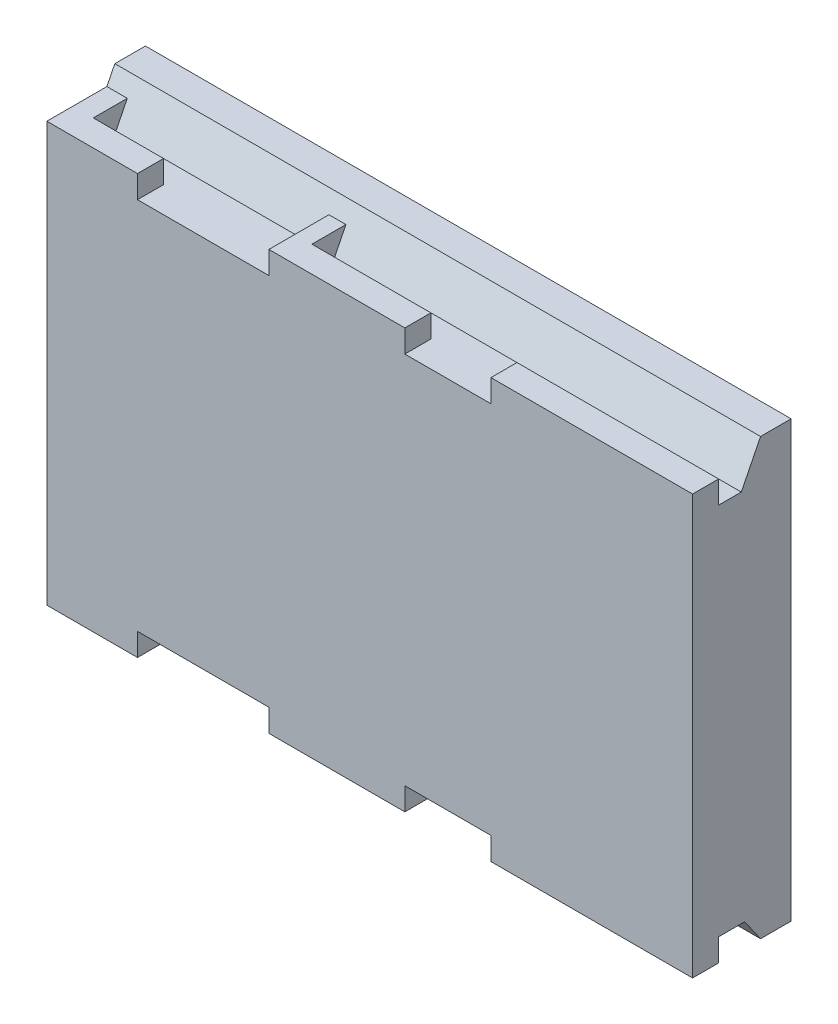
SolidWorks part; units mm, degrees
ref_plane "Спереди" through (0, 0, 0) normal (0, 0, 1) x (1, 0, 0)
ref_plane "Сверху" through (0, 0, 0) normal (0, 1, 0) x (1, 0, 0)
ref_plane "Справа" through (0, 0, 0) normal (1, 0, 0) x (0, 0, -1)
sketch "Эскиз1" plane through (0, 0, 0) normal (0, 0, 1) x (1, 0, 0)
  line L1 (0, 0) -> (57, 0)
  line L2 (0, 0) -> (0, 38.4)
  line L3 (0, 38.4) -> (57, 38.4)
  line L4 (57, 0) -> (57, 38.4)
  dimension "D1" = 57
  dimension "D2" = 38.4
extrude "Бобышка-Вытянуть1" add sketch "Эскиз1" along normal blind 8.7
sketch "Эскиз2" plane through (0, 0, 8.7) normal (0, 0, 1) x (1, 0, 0)
  line L0 (57, 0) -> (57, 38.4) construction
  line L1 (0, 38.4) -> (57, 38.4)
  line L2 (0, 38.4) -> (0, 37)
  line L3 (0, 37) -> (57, 37)
  line L4 (57, 38.4) -> (57, 37)
  line L5 (0, 0) -> (57, 0) construction
  dimension "D1" = 37
extrude "Вырез-Вытянуть1" cut sketch "Эскиз2" against normal blind 2.3
sketch "Эскиз3" plane through (0, 0, 0) normal (0, 1, 0) x (1, 0, 0)
  line L0 (57, -6.4) -> (57, 0) construction
  line L1 (0, -6.4) -> (57, -6.4)
  line L2 (0, -6.4) -> (0, -4.1)
  line L3 (0, -4.1) -> (57, -4.1)
  line L4 (57, -6.4) -> (57, -4.1)
  dimension "D1" = 2.3
extrude "Вырез-Вытянуть2" cut sketch "Эскиз3" along normal blind 2
sketch "Эскиз4" plane through (0, 0, 8.7) normal (0, 0, 1) x (1, 0, 0)
  line L0 (0, 0) -> (57, 0) construction
  line L1 (8, 0) -> (19.6, 0)
  line L2 (8, 0) -> (8, 2)
  line L3 (8, 2) -> (19.6, 2)
  line L4 (19.6, 0) -> (19.6, 2)
  line L5 (0, 2) -> (57, 2) construction
  line L6 (31.6, 0) -> (39.2, 0)
  line L7 (31.6, 0) -> (31.6, 2)
  line L8 (31.6, 2) -> (39.2, 2)
  line L9 (39.2, 0) -> (39.2, 2)
  line L10 (0, 37) -> (0, 0) construction
  line L11 (0, 18.5) -> (28.0003, 18.5) construction
  line L12 (39.2, 37) -> (39.2, 35)
  line L13 (31.6, 35) -> (39.2, 35)
  line L14 (31.6, 37) -> (31.6, 35)
  line L15 (31.6, 37) -> (39.2, 37)
  line L16 (19.6, 37) -> (19.6, 35)
  line L17 (8, 35) -> (19.6, 35)
  line L18 (8, 37) -> (8, 35)
  line L19 (8, 37) -> (19.6, 37)
  dimension "D1" = 8
  dimension "D2" = 11.6
  dimension "D3" = 12
  dimension "D4" = 7.6
extrude "Вырез-Вытянуть3" cut sketch "Эскиз4" against normal up to surface (2.3 mm away) up to face at (28.5, 1, 6.4)
sketch "Эскиз5" plane through (57, 0, 0) normal (1, 0, 0) x (0, 0, -1)
  line L0 (-4.1, 0) -> (-4.1, 2)
  line L1 (-4.1, 2) -> (-2.7, 0)
  line L2 (-4.1, 0) -> (0, 0) construction
  line L3 (-2.7, 0) -> (-4.1, 0)
  line L4 (-8.7, 0) -> (-8.7, 37) construction
  line L5 (0, 19.2) -> (-12.3399, 19.2) construction
  line L6 (0, 0) -> (0, 38.4) construction
  line L7 (-2.7, 0) -> (-2.7, 42.4842) construction
  line L8 (-4.4, 35) -> (-2.7, 38.4)
  line L9 (-6.4, 37) -> (-6.4, 35)
  line L10 (-6.4, 35) -> (-4.4, 35)
  line L11 (-2.7, 38.4) -> (-6.4, 38.4)
  line L12 (-6.4, 38.4) -> (-6.4, 37)
  line L13 (-6.4, 38.4) -> (0, 38.4) construction
  dimension "D1" = 6
  dimension "D2" = 2
  dimension "D3" = 2
extrude "Вырез-Вытянуть4" cut sketch "Эскиз5" against normal through all
sketch "Эскиз6" plane through (0, 0, 0) normal (0, -1, 0) x (1, 0, 0)
  line L1 (19.6, 6.4) -> (21.1, 6.4)
  line L2 (19.6, 6.4) -> (19.6, 2.7)
  line L3 (19.6, 2.7) -> (21.1, 2.7)
  line L4 (21.1, 6.4) -> (21.1, 2.7)
  line L5 (0, 2.7) -> (57, 2.7) construction
  line L6 (0, 6.4) -> (1.8, 6.4)
  line L7 (0, 6.4) -> (0, 2.7)
  line L8 (0, 2.7) -> (1.8, 2.7)
  line L9 (1.8, 6.4) -> (1.8, 2.7)
  dimension "D1" = 1.5
  dimension "D2" = 1.8
extrude "Бобышка-Вытянуть2" add sketch "Эскиз6" against normal blind 2
sketch "Эскиз7" plane through (0, 37, 0) normal (0, 1, 0) x (1, 0, 0)
  line L0 (0, -2.7) -> (57, -2.7) construction
  line L1 (0, -6.4) -> (1.8, -6.4)
  line L2 (0, -6.4) -> (0, -2.7)
  line L3 (0, -2.7) -> (1.8, -2.7)
  line L4 (1.8, -6.4) -> (1.8, -2.7)
  line L6 (19.6, -6.4) -> (21.1, -6.4)
  line L7 (19.6, -6.4) -> (19.6, -2.7)
  line L8 (19.6, -2.7) -> (21.1, -2.7)
  line L9 (21.1, -6.4) -> (21.1, -2.7)
  dimension "D1" = 1.8
  dimension "D2" = 1.5
extrude "Бобышка-Вытянуть3" add sketch "Эскиз7" against normal blind 2
